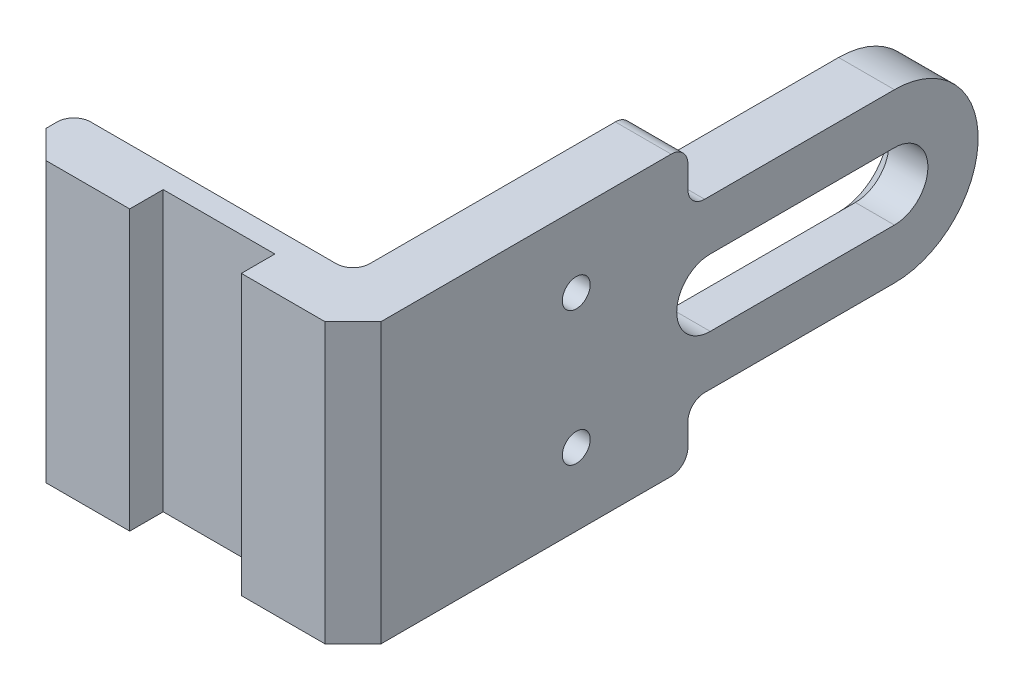
SolidWorks part; units mm, degrees
material "2014-T6"
ref_plane "Front Plane" through (0, 0, 0) normal (0, 0, 1) x (1, 0, 0)
ref_plane "Top Plane" through (0, 0, 0) normal (0, 1, 0) x (1, 0, 0)
ref_plane "Right Plane" through (0, 0, 0) normal (1, 0, 0) x (0, 0, -1)
sketch "Sketch1" plane through (0, 0, 0) normal (0, 1, 0) x (1, 0, 0)
  line L1 (0, 0) -> (-30, 0)
  line L2 (0, 0) -> (0, 10)
  line L3 (-5, 5) -> (-30, 5)
  line L4 (-30, 0) -> (-30, 5)
  line L5 (0, 0) -> (-5, 0)
  line L6 (0, 0) -> (0, 56)
  line L7 (0, 56) -> (-5, 56)
  line L8 (-5, 5) -> (-5, 56)
  dimension "D1" = 30
  dimension "D2" = 5
  dimension "D3" = 5
  dimension "D4" = 56
extrude "Boss-Extrude1" add sketch "Sketch1" along normal blind 25 contours L6 L7 L8 L3 L4 L1
sketch "Sketch2" plane through (0, 0, 0) normal (1, 0, 0) x (0, 0, -1)
  line L0 (0, 25) -> (56, 25) construction
  line L1 (30, 25) -> (56, 25)
  line L2 (30, 25) -> (30, 20)
  line L3 (30, 20) -> (56, 20)
  line L4 (56, 25) -> (56, 20)
  line L5 (56, 25) -> (56, 0) construction
  line L6 (0, 0) -> (56, 0) construction
  line L7 (30, 5) -> (56, 5)
  line L8 (30, 5) -> (30, 0)
  line L9 (30, 0) -> (56, 0)
  line L10 (56, 5) -> (56, 0)
  line L11 (0, 25) -> (0, 0) construction
  line L12 (0, 12.5) -> (97, 12.5) construction
  line L13 (56, 20) -> (56, 5)
  circle A0 centre (48.5, 12.5) radius 7.5
  dimension "D2" = 7.5
  dimension "D1" = 30
extrude "Cut-Extrude1" cut sketch "Sketch2" against normal blind 25 contours L4 L1 L2 L3 | A0 L13 L3 | A0 L7 L13 | L10 L7 L8 L9 region at (0, 22.5, -43) region at (0, 18.3247, -54.3247) region at (0, 6.6753, -54.3247) region at (0, 2.5, -43)
sketch "Sketch3" plane through (0, 0, 0) normal (1, 0, 0) x (0, 0, -1)
  line L0 (32, 12.5) -> (48.5, 12.5) construction
  line L1 (32, 15.5) -> (48.5, 15.5)
  line L2 (32, 9.5) -> (48.5, 9.5)
  line L3 (0, 12.5) -> (23.8442, 12.5) construction
  line L4 (0, 25) -> (0, 0) construction
  arc A0 (32, 15.5) -> (32, 9.5) centre (32, 12.5) ccw
  arc A1 (48.5, 9.5) -> (48.5, 15.5) centre (48.5, 12.5) ccw
  arc A2 (48.5, 5) -> (48.5, 20) centre (48.5, 12.5) ccw construction
  point P2 (40.25, 12.5)
  dimension "D1" = 3
  dimension "D2" = 32
  dimension "D3" = 48.5
extrude "Cut-Extrude2" cut sketch "Sketch3" against normal blind 25 contours L2 A1 L1 A0
fillet "Fillet1" radius 1.5 4 edges at (-2.5, 20, -30) (-2.5, 5, -30) (-2.5, 0, -30) (-2.5, 25, -30)
sketch "Sketch5" plane through (0, 0, 0) normal (1, 0, 0) x (0, 0, -1)
  line L0 (0, 0) -> (5, 0) construction
  line L1 (5, 25) -> (28.5, 25) construction
  circle A0 centre (20, 18.5) radius 3
  circle A1 centre (20, 6.5) radius 3
  circle A2 centre (20, 18.5) radius 1.25
  circle A3 centre (20, 6.5) radius 1.25
  dimension "D2" = 6
  dimension "D3" = 6
  dimension "D7" = 2.5
  dimension "D8" = 2.5
  dimension "D1" = 12
  dimension "D4" = 20
  dimension "D5" = 6.5
  dimension "D6" = 6.5
extrude "Cut-Extrude4" cut sketch "Sketch5" against normal blind 25 contours A2 | A3
extrude "Cut-Extrude5" cut sketch "Sketch5<4>" against normal blind 2.5 from offset 2.5 offset against normal yes
sketch "Sketch5<4>" plane through (0, 0, 0) normal (1, 0, 0) x (0, 0, -1) same geometry as "Sketch5"
sketch "Sketch7" plane through (0, 25, 0) normal (0, 1, 0) x (1, 0, 0)
  line L0 (0, 0) -> (-30, 0) construction
  line L1 (-20, 3) -> (-10, 3)
  line L2 (-20, 3) -> (-20, 0)
  line L3 (-20, 0) -> (-10, 0)
  line L4 (-10, 3) -> (-10, 0)
  line L5 (-30, 0) -> (-30, 5) construction
  dimension "D1" = 10
  dimension "D2" = 10
  dimension "D3" = 3
extrude "Cut-Extrude6" cut sketch "Sketch7" against normal through all contours L4 L3 L2 L1
chamfer "Chamfer1" distance 2.5 angle 45 2 edges at (0, 12.5, 0) (-30, 12.5, 0)
fillet "Fillet2" radius 1.5 2 edges at (-30, 12.5, -5) (-5, 12.5, -5)
chamfer "Chamfer2" distance 1.5 angle 45 4 edges at (-5, 9.5, -40.25) (-5, 12.5, -51.5) (-5, 12.5, -29) (-5, 15.5, -40.25)
